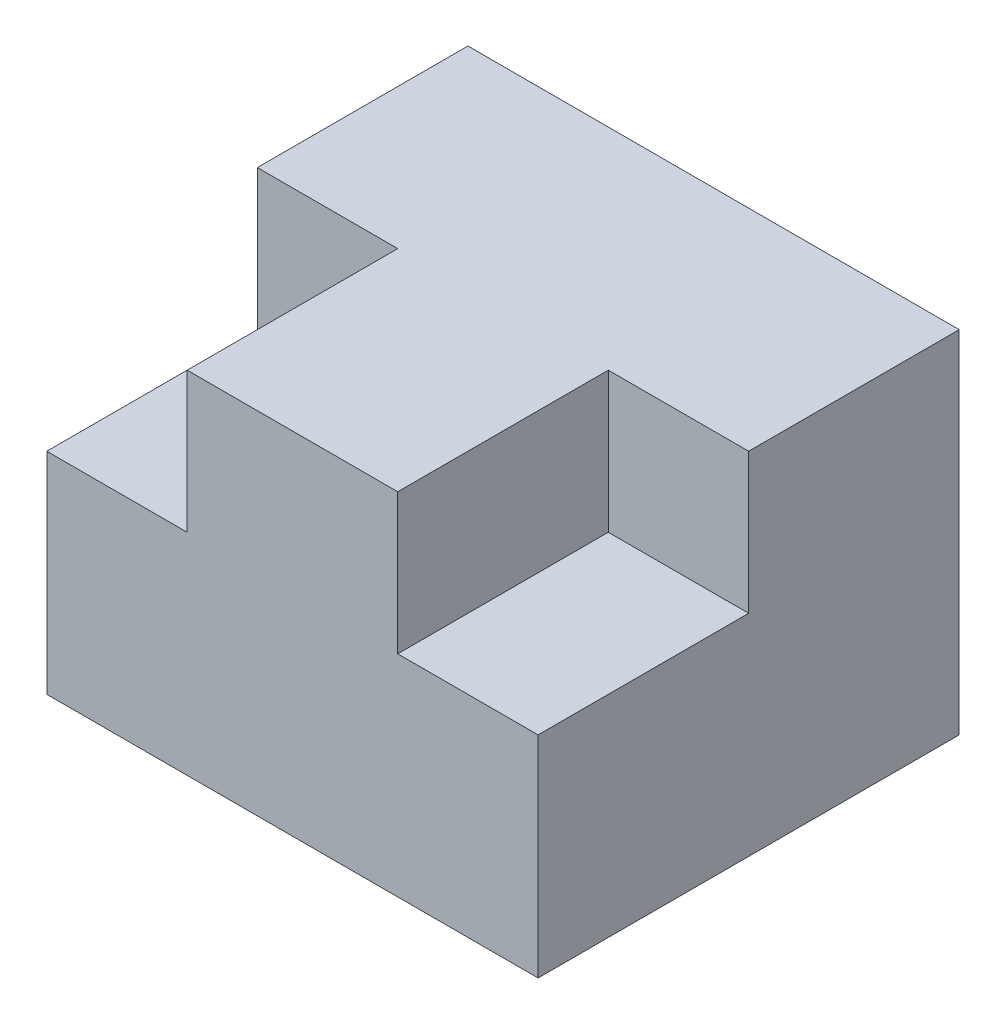
SolidWorks part; units mm, degrees
ref_plane "Front Plane" through (0, 0, 0) normal (0, 0, 1) x (1, 0, 0)
ref_plane "Top Plane" through (0, 0, 0) normal (0, 1, 0) x (1, 0, 0)
ref_plane "Right Plane" through (0, 0, 0) normal (1, 0, 0) x (0, 0, -1)
sketch "Sketch1" plane through (0, 0, 0) normal (0, 0, 1) x (1, 0, 0)
  line L1 (0, 0) -> (35, 0)
  line L2 (0, 0) -> (0, 25)
  line L3 (0, 25) -> (35, 25)
  line L4 (35, 0) -> (35, 25)
  line L5 (0, 25) -> (10, 25)
  line L6 (0, 25) -> (0, 15)
  line L7 (0, 15) -> (10, 15)
  line L8 (10, 25) -> (10, 15)
  line L9 (35, 25) -> (25, 25)
  line L10 (35, 25) -> (35, 15)
  line L11 (35, 15) -> (25, 15)
  line L12 (25, 25) -> (25, 15)
  dimension "D1" = 35
  dimension "D2" = 25
  dimension "D3" = 10
extrude "Boss-Extrude1" add sketch "Sketch1" along normal blind 15 contours L12 L3 L8 L7 L2 L1 L4 L11 | L8 L3 L2 L7 | L3 L12 L11 L4 region at (17.5, 10.2778, 0) region at (5, 20, 0) region at (30, 20, 0)
extrude "Boss-Extrude2" add sketch "Sketch1<3>" along normal blind 30 contours L12 L3 L8 L7 L2 L1 L4 L11 region at (17.5, 10.2778, 0)
sketch "Sketch1<3>" plane through (0, 0, 0) normal (0, 0, 1) x (1, 0, 0) same geometry as "Sketch1"
